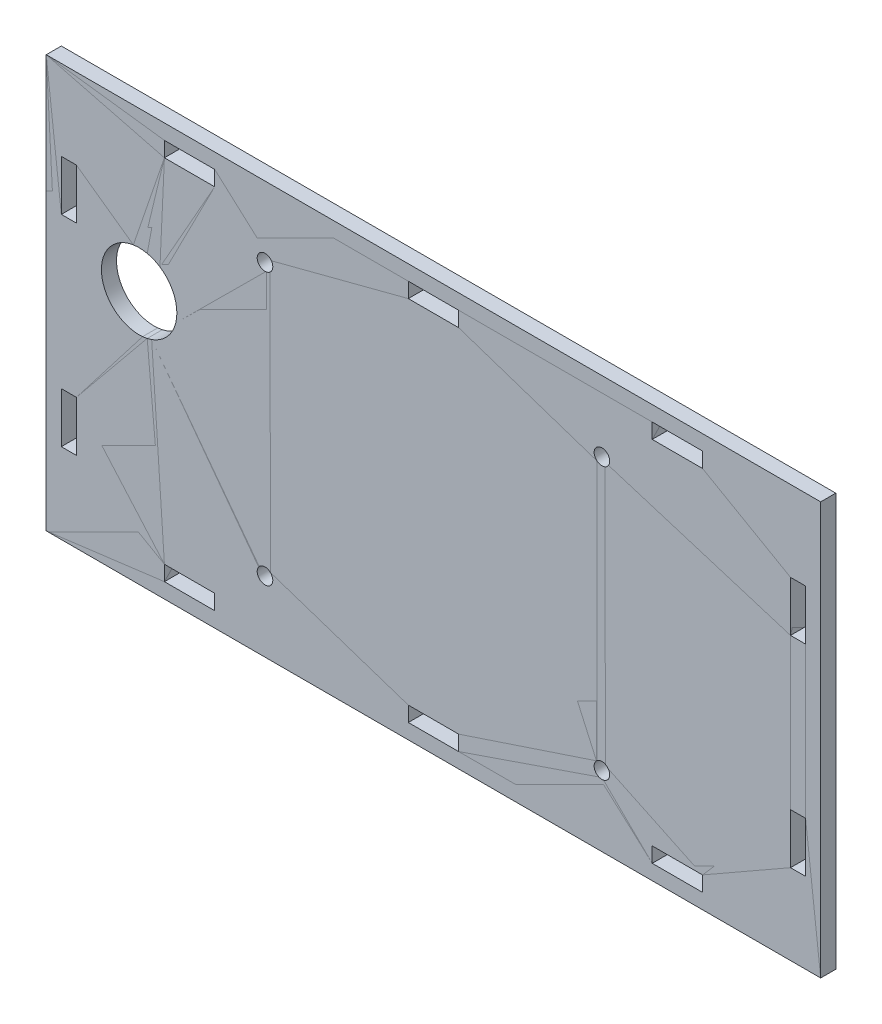
SolidWorks part; units mm, degrees
ref_plane "前视基准面" through (0, 0, 0) normal (0, 0, 1) x (1, 0, 0)
ref_plane "上视基准面" through (0, 0, 0) normal (0, 1, 0) x (1, 0, 0)
ref_plane "右视基准面" through (0, 0, 0) normal (1, 0, 0) x (0, 0, -1)
sketch "草图1" plane through (0, 0, 0) normal (0, 0, 1) x (1, 0, 0)
  line L0 (0, -9.5012) -> (46.4632, -9.5012) construction
  line L1 (-77, 31.4988) -> (77, 31.4988)
  line L2 (-77, 31.4988) -> (-77, -50.5012)
  line L3 (-77, -50.5012) -> (77, -50.5012)
  line L4 (77, 31.4988) -> (77, -50.5012)
  line L5 (-77, 31.4988) -> (77, -50.5012) construction
  line L6 (-77, -50.5012) -> (77, 31.4988) construction
  line L7 (-74, -24.5012) -> (-71, -24.5012)
  line L8 (-74, -24.5012) -> (-74, -34.5012)
  line L9 (-74, -34.5012) -> (-71, -34.5012)
  line L10 (-71, -24.5012) -> (-71, -34.5012)
  line L11 (-74, -24.5012) -> (-71, -34.5012) construction
  line L12 (-74, -34.5012) -> (-71, -24.5012) construction
  line L17 (-53.5, -44.5012) -> (-43.5, -44.5012)
  line L18 (-53.5, -44.5012) -> (-53.5, -47.5012)
  line L19 (-5, -44.5012) -> (5, -44.5012)
  line L20 (-5, -44.5012) -> (-5, -47.5012)
  line L21 (-5, -47.5012) -> (5, -47.5012)
  line L22 (5, -44.5012) -> (5, -47.5012)
  line L23 (-5, -44.5012) -> (5, -47.5012) construction
  line L24 (-5, -47.5012) -> (5, -44.5012) construction
  line L25 (-53.5, -47.5012) -> (-43.5, -47.5012)
  line L26 (-43.5, -44.5012) -> (-43.5, -47.5012)
  line L27 (-53.5, -44.5012) -> (-43.5, -47.5012) construction
  line L28 (-53.5, -47.5012) -> (-43.5, -44.5012) construction
  line L29 (0, -9.5012) -> (0, -75.1961) construction
  line L30 (-5, 28.4988) -> (5, 28.4988)
  line L31 (5, 25.4988) -> (5, 28.4988)
  line L32 (-5, 25.4988) -> (5, 25.4988)
  line L33 (-5, 25.4988) -> (-5, 28.4988)
  line L34 (-53.5, 28.4988) -> (-43.5, 28.4988)
  line L35 (-43.5, 25.4988) -> (-43.5, 28.4988)
  line L36 (-53.5, 25.4988) -> (-43.5, 25.4988)
  line L37 (-53.5, 25.4988) -> (-53.5, 28.4988)
  line L38 (-74, 15.4988) -> (-71, 15.4988)
  line L39 (-71, 5.4988) -> (-71, 15.4988)
  line L40 (-74, 5.4988) -> (-71, 5.4988)
  line L41 (-74, 5.4988) -> (-74, 15.4988)
  line L42 (53.5, -47.5012) -> (43.5, -47.5012)
  line L43 (43.5, -44.5012) -> (43.5, -47.5012)
  line L44 (53.5, -44.5012) -> (43.5, -44.5012)
  line L45 (53.5, -44.5012) -> (53.5, -47.5012)
  line L46 (74, -34.5012) -> (71, -34.5012)
  line L47 (71, -24.5012) -> (71, -34.5012)
  line L48 (74, -24.5012) -> (71, -24.5012)
  line L49 (74, -24.5012) -> (74, -34.5012)
  line L50 (74, 5.4988) -> (74, 15.4988)
  line L51 (74, 5.4988) -> (71, 5.4988)
  line L52 (71, 5.4988) -> (71, 15.4988)
  line L53 (74, 15.4988) -> (71, 15.4988)
  line L54 (53.5, 25.4988) -> (53.5, 28.4988)
  line L55 (53.5, 25.4988) -> (43.5, 25.4988)
  line L56 (43.5, 25.4988) -> (43.5, 28.4988)
  line L57 (53.5, 28.4988) -> (43.5, 28.4988)
  circle A0 centre (-33.5, 17.5) radius 1.55
  circle A1 centre (-33.5, -36.5025) radius 1.55
  circle A2 centre (33.5, -36.5025) radius 1.55
  circle A3 centre (33.5, 17.5) radius 1.55
  circle A4 centre (-58.5266, 0) radius 7.5
  point P0 (0, -9.5012)
  point P5 (-72.5, -29.5012)
  point P10 (-43.7493, -32.7964)
  point P11 (-45.5, -46.0012)
  point P15 (0, -46.0012)
  point P34 (-48.5, -46.0012)
  point P63 (0, 0)
  dimension "D9" = 3.1
  dimension "D10" = 15
  dimension "D1" = 154
  dimension "D2" = 82
  dimension "D3" = 3
  dimension "D4" = 10
  dimension "D5" = 3
  dimension "D6" = 16
  dimension "D7" = 3
  dimension "D8" = 23.5
extrude "凸台-拉伸2" add sketch "草图1<2>" along normal blind 3
sketch "草图1<2>" plane through (0, 0, 0) normal (0, 0, 1) x (1, 0, 0) same geometry as "草图1"
extrude "凸台-拉伸1" add sketch "草图1" along normal blind 3
